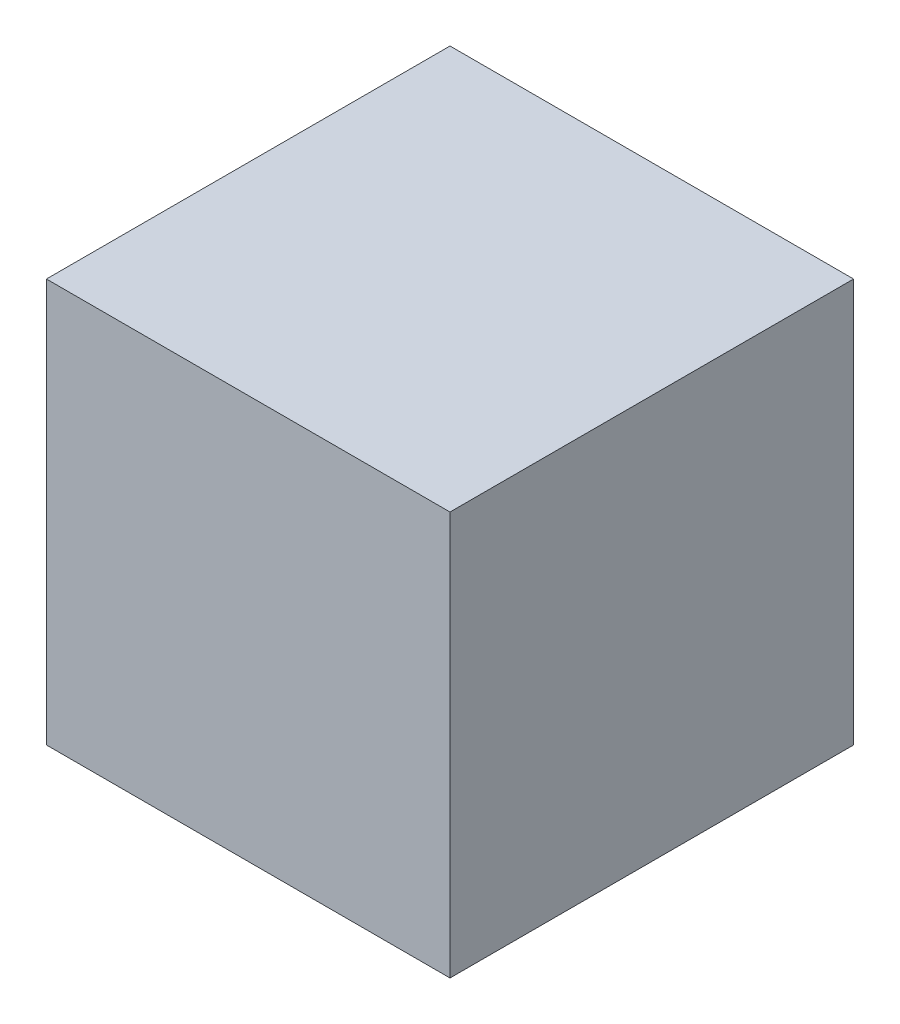
SolidWorks part; units mm, degrees
ref_plane "Front Plane" through (0, 0, 0) normal (0, 0, 1) x (1, 0, 0)
ref_plane "Top Plane" through (0, 0, 0) normal (0, 1, 0) x (1, 0, 0)
ref_plane "Right Plane" through (0, 0, 0) normal (1, 0, 0) x (0, 0, -1)
sketch "Sketch1" plane through (0, 0, 0) normal (0, 1, 0) x (1, 0, 0)
  line L1 (-28, -28) -> (28, -28)
  line L2 (-28, -28) -> (-28, 28)
  line L3 (-28, 28) -> (28, 28)
  line L4 (28, -28) -> (28, 28)
  line L5 (-28, -28) -> (28, 28) construction
  line L6 (-28, 28) -> (28, -28) construction
  point P0 (0, 0)
  dimension "D1" = 56
  dimension "D2" = 56
extrude "Boss-Extrude1" add sketch "Sketch1" along normal blind 28 and the other way blind 28
ref_axis "X" through (-30.8, 0, 0) along (1, 0, 0)
ref_axis "Y" through (0, 30.8, 0) along (0, -1, 0)
ref_axis "Z" through (0, 0, -30.8) along (0, 0, 1)
ref_plane "+Z" through (0, 0, 0) normal (0, 0, 1) x (1, 0, 0)
ref_plane "+Y" through (0, 0, 0) normal (0, 1, 0) x (1, 0, 0)
ref_plane "+X" through (0, 0, 0) normal (1, 0, 0) x (0, 0, -1)
ref_plane "+Z +Y" through (0, 0, 0) normal (0, -0.7071, 0.7071) x (1, 0, 0)
ref_plane "+Z -Y" through (0, 0, 0) normal (0, 0.7071, 0.7071) x (1, 0, 0)
ref_plane "+Z +X" through (0, 0, 0) normal (0.7071, 0, 0.7071) x (0.7071, 0, -0.7071)
ref_plane "+Z -X" through (0, 0, 0) normal (-0.7071, 0, 0.7071) x (0.7071, 0, 0.7071)
ref_plane "+Y +X" through (0, 0, 0) normal (0.7071, 0.7071, 0) x (0.7071, -0.7071, 0)
ref_plane "+Y -X" through (0, 0, 0) normal (-0.7071, 0.7071, 0) x (0.7071, 0.7071, 0)
ref_axis "X Y Z" through (-55, -55, -55) along (0.5774, 0.5774, 0.5774)
ref_axis "-X Y Z" through (-55, 55, 55) along (0.5774, -0.5774, -0.5774)
ref_axis "X -Y Z" through (55, -55, 55) along (-0.5774, 0.5774, -0.5774)
ref_axis "X Y -Z" through (55, 55, -55) along (-0.5774, -0.5774, 0.5774)
ref_plane "+Z +Y +X" through (0, 0, 0) normal (0.5774, 0.5774, 0.5774) x (0.8165, -0.4082, -0.4082)
ref_plane "+Z +Y -X" through (0, 0, 0) normal (-0.5774, 0.5774, 0.5774) x (0.8165, 0.4082, 0.4082)
ref_plane "+Z -Y +X" through (0, 0, 0) normal (0.5774, -0.5774, 0.5774) x (-0.8165, -0.4082, 0.4082)
ref_plane "-Z +Y +X" through (0, 0, 0) normal (0.5774, 0.5774, -0.5774) x (0.8165, -0.4082, 0.4082)
equation "\"Edge_Length\"= 56mm"
